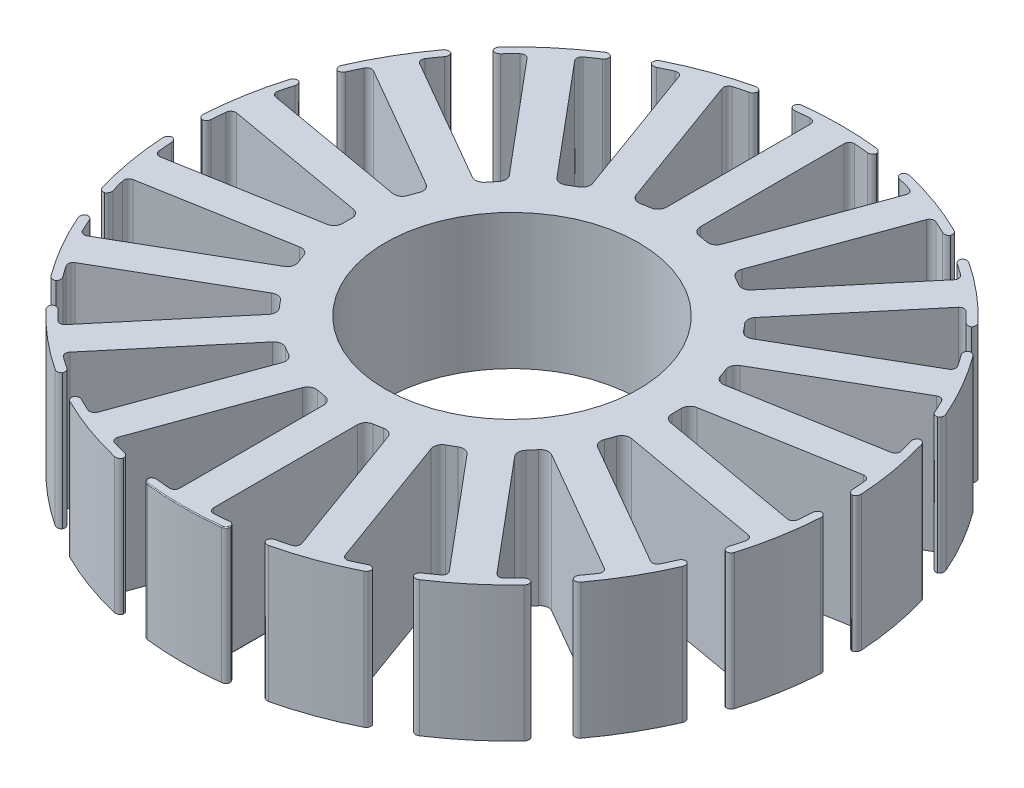
SolidWorks part; units mm, degrees
material "Ductile Iron"
ref_plane "Front Plane" through (0, 0, 0) normal (0, 0, 1) x (1, 0, 0)
ref_plane "Top Plane" through (0, 0, 0) normal (0, 1, 0) x (1, 0, 0)
ref_plane "Right Plane" through (0, 0, 0) normal (1, 0, 0) x (0, 0, -1)
sketch "Sketch1" plane through (0, 0, 0) normal (0, 1, 0) x (1, 0, 0)
  circle A1 centre (0, 0) radius 9.75
  dimension "D1" = 19.5
extrude "Boss-Extrude1" add sketch "Sketch1" along normal mid plane 8
ref_axis "Axis1" through (0, 4, 0) along (0, -1, 0)
sketch "Sketch2" plane through (0, 4, 0) normal (0, 1, 0) x (1, 0, 0)
  line L0 (0, 0) -> (0, 19.5) construction
  line L1 (-2.5, 19.3391) -> (-2.4359, 18.8432)
  line L2 (2.5, 19.3391) -> (2.4359, 18.8432)
  line L3 (-1, 18.9737) -> (-1, 9.6986)
  line L4 (1, 18.9737) -> (1, 9.6986)
  circle A0 centre (0, 0) radius 9.75 construction
  arc A1 (1, 9.6986) -> (-1, 9.6986) centre (0, 0) ccw
  arc A2 (2.5, 19.3391) -> (-2.5, 19.3391) centre (0, 0) ccw
  arc A3 (2.4359, 18.8432) -> (1, 18.9737) centre (0, 0) ccw
  arc A4 (-1, 18.9737) -> (-2.4359, 18.8432) centre (0, 0) ccw
  dimension "D1" = 19.5
  dimension "D2" = 0.5
  dimension "D3" = 2
  dimension "D4" = 5
extrude "Boss-Extrude2" add sketch "Sketch2" against normal up to surface (8 mm away) up to face at (0, -4, 9.75)
fillet "Fillet1" radius 0.3 6 edges at (-1, 0, -18.9737) (1, 0, -18.9737) (2.5, 0, -19.3391) (2.4359, 0, -18.8432) (-2.5, 0, -19.3391) (-2.4359, 0, -18.8432)
pattern_circular "CirPattern1" count 18 over 360 about axis through (0, 4, 0) along (0, -1, 0) of "Boss-Extrude2", "Fillet1"
fillet "Fillet2" radius 0.5 36 edges at (-5.4681, 0, 8.0723) (-4.2568, 0, 8.7717) (-2.3774, 0, 9.4557) (-1, 0, 9.6986) (1, 0, 9.6986) (2.3774, 0, 9.4557) (4.2568, 0, 8.7717) (5.4681, 0, 8.0723) (7.0002, 0, 6.7868) (7.8992, 0, 5.7153) (8.8992, 0, 3.9833) (9.3776, 0, 2.6689) (9.7249, 0, 0.6993) (9.7249, 0, -0.6993) (9.3776, 0, -2.6689) (8.8992, 0, -3.9833) (7.0002, 0, -6.7868) (-7.0002, 0, 6.7868) (1, 0, -9.6986) (4.2568, 0, -8.7717) (7.8992, 0, -5.7153) (5.4681, 0, -8.0723) (2.3774, 0, -9.4557) (-1, 0, -9.6986) (-4.2568, 0, -8.7717) (-2.3774, 0, -9.4557) (-7.0002, 0, -6.7868) (-5.4681, 0, -8.0723) (-8.8992, 0, -3.9833) (-7.8992, 0, -5.7153) (-9.7249, 0, -0.6993) (-9.3776, 0, -2.6689) (-9.3776, 0, 2.6689) (-9.7249, 0, 0.6993) (-8.8992, 0, 3.9833) (-7.8992, 0, 5.7153)
sketch "Sketch3" plane through (0, 4, 0) normal (0, 1, 0) x (1, 0, 0)
  circle A0 centre (0, 0) radius 7.5
  dimension "D1" = 15
extrude "Cut-Extrude1" cut sketch "Sketch3" against normal through all
fillet "Fillet3" radius 0.05 14 edges at (5.426, -4, 18.1105) (4.8436, -4, 18.3723) (4.2731, -4, 18.5854) (2.3412, -4, 18.9261) (1.7322, -4, 18.9209) (1.0954, -4, 18.8741) (1, -4, 14.3972) (1.1215, -4, 9.813) (1.6931, -4, 9.6019) (2.3024, -4, 9.6048) (-2.3836, 4, 19.2818) (2.3836, 4, 19.2818) (3.9844, -4, 13.871) (0, 4, 19.5)
